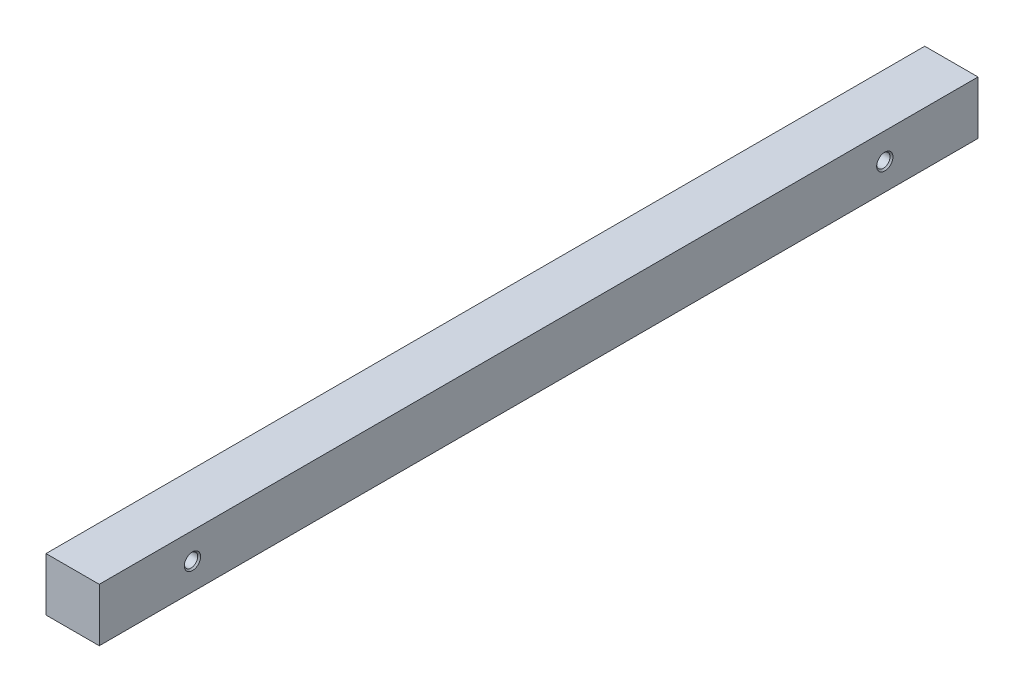
SolidWorks part; units mm, degrees
ref_plane "Plan de face" through (0, 0, 0) normal (0, 0, 1) x (1, 0, 0)
ref_plane "Plan de dessus" through (0, 0, 0) normal (0, 1, 0) x (1, 0, 0)
ref_plane "Plan de droite" through (0, 0, 0) normal (1, 0, 0) x (0, 0, -1)
sketch "Esquisse1" plane through (0, 0, 0) normal (0, 0, 1) x (1, 0, 0)
  line L0 (-5, 5) -> (5, -5) construction
  line L1 (-5, 5) -> (5, 5)
  line L2 (-5, 5) -> (-5, -5)
  line L3 (-5, -5) -> (5, -5)
  line L4 (5, 5) -> (5, -5)
  dimension "D1" = 10
extrude "Boss.-Extru.1" add sketch "Esquisse1" along normal mid plane 165
hole_wizard "Trou taraudé M3x0.51" positions "Esquisse3" profile "Esquisse2" tap size "M3x0.5" standard "Ansi Metric" end condition through all
sketch "Esquisse3" plane through (5, 0, 0) normal (1, 0, 0) x (0, 0, -1)
  point P0 (65, 0)
  point P3 (-65, 0)
sketch "Esquisse2" plane through (5, 0, -65) normal (0, 1, 0) x (0, 0, -1)
  line L0 (0, 0) -> (0, 10)
  line L1 (0, 10) -> (1.25, 10)
  line L2 (1.25, 10) -> (1.25, 0.275)
  line L3 (1.25, 0.275) -> (1.525, 0)
  line L5 (1.525, 0) -> (0, 0)
  line L6 (-1.25, 0.275) -> (-1.525, 0) construction
  line L11 (0, -6.35) -> (0, 107.95) construction
  dimension "Diamètre du trou pour taraudage jusqu'au prochain" = 2.5
  dimension "Profondeur du trou pour taraudage jusqu'au prochain" = 10
  dimension "Diamètre du fraisage entrant" = 3.05
  dimension "Angle du fraisage entrant" = 90
cosmetic thread "Filetage de perçage1"
cosmetic thread "Filetage de perçage2"
